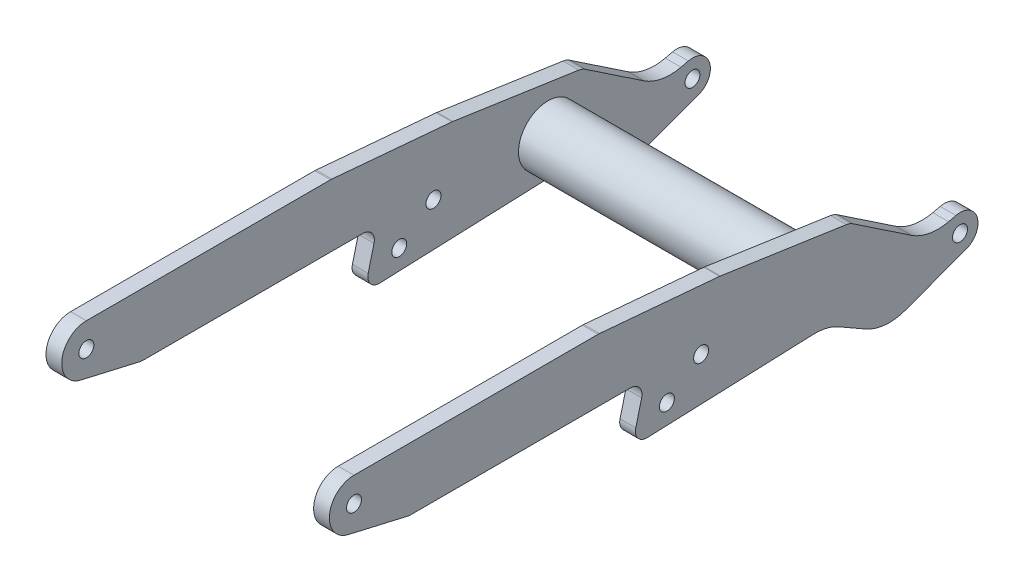
SolidWorks part; units mm, degrees
ref_plane "Front Plane" through (0, 0, 0) normal (0, 0, 1) x (1, 0, 0)
ref_plane "Top Plane" through (0, 0, 0) normal (0, 1, 0) x (1, 0, 0)
ref_plane "Right Plane" through (0, 0, 0) normal (1, 0, 0) x (0, 0, -1)
sketch "Sketch1" plane through (0, 0, 0) normal (1, 0, 0) x (0, 0, -1)
  line L0 (0, 0) -> (91.7084, 0) construction
  line L1 (0, 3.13) -> (31.1, 3.13)
  line L2 (31.1, 3.13) -> (46.5, 1.7827)
  line L3 (46.5, 1.7827) -> (63, -0.6391)
  line L4 (70.8309, -5.8913) -> (63, -0.6391)
  line L5 (76.4794, -6.5302) -> (75.5429, -6.7499)
  line L6 (-0.7041, -3.0498) -> (7, -4.8284)
  line L7 (7, -4.8284) -> (35.1369, -4.8284)
  line L8 (36.5425, -6.6345) -> (35.7999, -9.5658)
  line L9 (37.2618, -11.3708) -> (58.3808, -10.5504)
  line L10 (61.5933, -11.338) -> (65.0314, -13.3051)
  line L11 (70.0852, -13.7273) -> (77.7882, -10.8894)
  circle A0 centre (0, 0) radius 0.95
  circle A1 centre (44.1, -5.6) radius 0.95
  circle A2 centre (39.75, -8.75) radius 0.95
  circle A3 centre (77, -8.75) radius 0.95
  arc A4 (0, 3.13) -> (-0.7041, -3.0498) centre (0, 0) ccw
  arc A5 (76.4794, -6.5302) -> (77.7882, -10.8894) centre (77, -8.75) cw
  arc A6 (58.3808, -10.5504) -> (61.5933, -11.338) centre (58.6137, -16.5459) cw
  arc A7 (65.0314, -13.3051) -> (70.0852, -13.7273) centre (68.011, -8.0972) ccw
  arc A8 (75.5429, -6.7499) -> (70.8309, -5.8913) centre (74.173, -0.9083) cw
  arc A9 (35.1369, -4.8284) -> (36.5425, -6.6345) centre (35.1369, -6.2784) cw
  arc A10 (35.7999, -9.5658) -> (37.2618, -11.3708) centre (37.2055, -9.9218) ccw
  point P11 (45.8542, 0)
  point P26 (60.1, -10.4836)
  point P31 (73, -7.3462)
  point P34 (37, -4.8284)
  dimension "D1" = 1.9
  dimension "D2" = 1.9
  dimension "D3" = 39.75
  dimension "D4" = 44.1
  dimension "D5" = 77
  dimension "D6" = 5.6
  dimension "D7" = 8.75
  dimension "D8" = 8.75
  dimension "D9" = 3.13
  dimension "D10" = 2.28
  dimension "D22" = 16
  dimension "D25" = 6
  dimension "D26" = 1.45
  dimension "D27" = 6
  dimension "D28" = 1.45
  dimension "D11" = 31.1
  dimension "D12" = 46.5
  dimension "D13" = 63
  dimension "D14" = 175
  dimension "D15" = 176.65
  dimension "D16" = 154.5
  dimension "D17" = 10
  dimension "D18" = 7
  dimension "D19" = 167
  dimension "D20" = 30
  dimension "D21" = 73.56
  dimension "D23" = 148
  dimension "D24" = 130
extrude "Boss-Extrude1" add sketch "Sketch1" along normal mid plane 36
fillet "Fillet1" radius 2 4 edges at (0, -4.8284, -7) (0, -0.6391, -63) (0, 1.7827, -46.5) (0, 3.13, -31.1)
sketch "Sketch2" plane through (0, 0, 0) normal (0, 1, 0) x (1, 0, 0)
  line L0 (-18, -3.13) -> (18, -3.13) construction
  line L1 (-16, -3.13) -> (16, -3.13)
  line L2 (-16, -3.13) -> (-16, 79.28)
  line L3 (-16, 79.28) -> (16, 79.28)
  line L4 (16, -3.13) -> (16, 79.28)
  line L5 (18, 79.28) -> (-18, 79.28) construction
  line L6 (18, 31.0127) -> (18, 0) construction
  line L7 (-18, 62.5522) -> (-18, 46.5579) construction
  dimension "D1" = 2
  dimension "D2" = 2
extrude "Cut-Extrude1" cut sketch "Sketch2" against normal through all both and the other way through all
sketch "Sketch3" plane through (0, 0, 0) normal (1, 0, 0) x (0, 0, -1)
  circle A0 centre (58.65, -5.75) radius 3.75
  dimension "D1" = 7.5
  dimension "D2" = 58.65
  dimension "D3" = 5.75
extrude "Boss-Extrude2" add sketch "Sketch3" along normal up to next (16 mm away) and the other way up to next (16 mm away)
